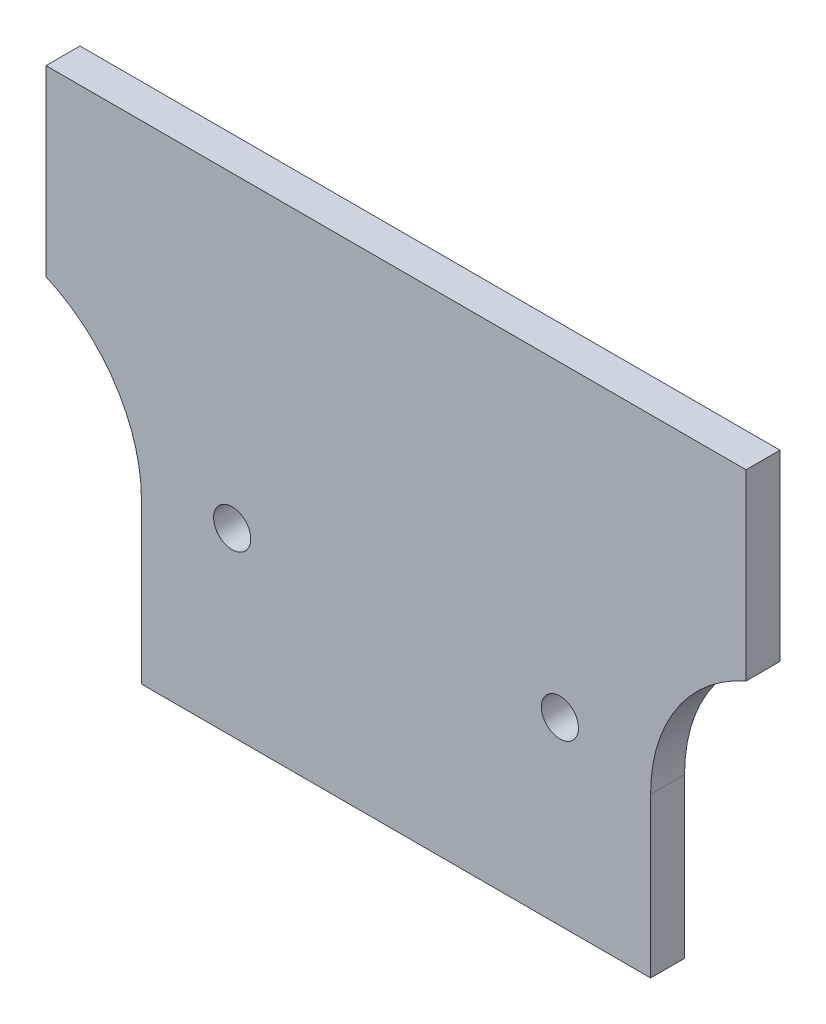
SolidWorks part; units mm, degrees
ref_plane "Front Plane" through (0, 0, 0) normal (0, 0, 1) x (1, 0, 0)
ref_plane "Top Plane" through (0, 0, 0) normal (0, 1, 0) x (1, 0, 0)
ref_plane "Right Plane" through (0, 0, 0) normal (1, 0, 0) x (0, 0, -1)
ref_axis "Axis1" through (0, 0, 0) along (0, 1, 0)
ref_plane "Camera Mount Plane" through (0, 0, 0.8128) normal (0, 0, 1) x (1, 0, 0)
sketch "Sketch1" plane through (0, 0, 0) normal (0, 0, 1) x (1, 0, 0)
  line L0 (5.715, 0) -> (-5.715, 0) construction
  line L2 (-5.715, -3.81) -> (-5.715, 5.08)
  line L3 (-5.715, 5.08) -> (5.715, 5.08)
  line L4 (5.715, -3.81) -> (5.715, 5.08)
  line L5 (0, 5.08) -> (0, -3.81) construction
  line L7 (5.715, -3.81) -> (-5.715, -3.81)
  circle A0 centre (-3.9243, 0.508) radius 0.445
  circle A1 centre (3.9243, 0.508) radius 0.445
  dimension "D1" = 0.508
  dimension "D5" = 0.89
  dimension "D2" = 7.8486
  dimension "D3" = 11.43
  dimension "D4" = 5.08
  dimension "D8" = 3.81
sketch "Sketch3" plane through (0, 0, 0) normal (0, 0, 1) x (1, 0, 0)
  line L0 (8.382, 7.874) -> (-8.382, 7.874)
  line L1 (-8.382, 7.874) -> (-8.382, 3.4919)
  line L2 (-6.096, 0) -> (-6.096, -3.81)
  line L3 (-6.096, -3.81) -> (6.096, -3.81)
  line L4 (0, 7.874) -> (0, 0) construction
  line L5 (6.096, 0) -> (6.096, -3.81)
  line L6 (8.382, 7.874) -> (8.382, 3.4919)
  line L7 (7.874, 7.112) -> (7.874, 3.912)
  line L8 (-7.874, 7.112) -> (-3.874, 7.112)
  line L9 (-7.874, 7.112) -> (-7.874, 3.912)
  line L10 (-7.874, 3.912) -> (-3.874, 3.912)
  line L11 (-3.874, 7.112) -> (-3.874, 3.912)
  line L12 (7.874, 7.112) -> (3.874, 7.112)
  line L13 (3.874, 7.112) -> (3.874, 3.912)
  line L14 (7.874, 3.912) -> (3.874, 3.912)
  line L16 (5.715, -3.81) -> (-5.715, -3.81) construction
  arc A0 (-8.382, 3.4919) -> (-6.096, 0) centre (-9.906, 0) cw
  arc A1 (8.382, 3.4919) -> (6.096, 0) centre (9.906, 0) ccw
  circle A2 centre (-9.906, 0) radius 3.175 construction
  circle A3 centre (9.906, 0) radius 3.175 construction
  dimension "D5" = 6.35
  dimension "D6" = 3.81
  dimension "D7" = 0.635
  dimension "D1" = 4
  dimension "D2" = 3.2
  dimension "D3" = 0.762
  dimension "D4" = 9.906
  dimension "D8" = 7.874
  dimension "D9" = 0.508
  dimension "D10" = 16.764
sketch "Sketch2" plane through (0, 0, 0) normal (0, 0, 1) x (1, 0, 0)
  line L0 (-5.715, -3.81) -> (-5.715, 5.08)
  line L1 (5.715, -3.81) -> (5.715, 5.08)
  line L8 (5.715, -3.81) -> (-5.715, -3.81) construction
  line L14 (-5.715, 5.08) -> (5.715, 5.08) construction
  line L16 (5.715, -3.81) -> (-5.715, -3.81)
  line L22 (-5.715, 5.08) -> (5.715, 5.08)
  circle A0 centre (-3.9243, 0.508) radius 0.445 construction
  circle A1 centre (-3.9243, 0.508) radius 0.445
  circle A2 centre (3.9243, 0.508) radius 0.445 construction
  circle A3 centre (3.9243, 0.508) radius 0.445
extrude "Boss-Extrude1" add sketch "Sketch2" along normal up to surface (0.8128 mm away) up to plane "Camera Mount Plane"
sketch "Sketch4" plane through (0, 0, 0) normal (0, 0, 1) x (1, 0, 0)
  line L6 (8.382, 7.874) -> (-8.382, 7.874)
  line L7 (-8.382, 7.874) -> (-8.382, 3.4919)
  line L8 (-6.096, 0) -> (-6.096, -3.81)
  line L9 (-6.096, -3.81) -> (6.096, -3.81)
  line L10 (6.096, -3.81) -> (6.096, 0)
  line L11 (8.382, 3.4919) -> (8.382, 7.874)
  line L12 (8.382, 7.874) -> (-8.382, 7.874)
  line L13 (-8.382, 7.874) -> (-8.382, 3.4919)
  line L14 (-6.096, 0) -> (-6.096, -3.81)
  line L15 (-6.096, -3.81) -> (6.096, -3.81)
  line L16 (6.096, -3.81) -> (6.096, 0)
  line L17 (8.382, 3.4919) -> (8.382, 7.874)
  circle A0 centre (-3.9243, 0.508) radius 0.445 construction
  circle A1 centre (-3.9243, 0.508) radius 0.445
  arc A2 (-6.096, 0) -> (-8.382, 3.4919) centre (-9.906, 0) ccw
  arc A3 (8.382, 3.4919) -> (6.096, 0) centre (9.906, 0) ccw
  arc A4 (-6.096, 0) -> (-8.382, 3.4919) centre (-9.906, 0) ccw
  arc A5 (8.382, 3.4919) -> (6.096, 0) centre (9.906, 0) ccw
  circle A6 centre (3.9243, 0.508) radius 0.445 construction
  circle A7 centre (3.9243, 0.508) radius 0.445
  dimension "D1" = 0
extrude "Boss-Extrude2" add sketch "Sketch4" along normal up to surface (0.8128 mm away) up to plane "Camera Mount Plane"
sketch "Sketch5" plane through (0, 0, 0.8128) normal (0, 0, 1) x (1, 0, 0)
  line L0 (-7.874, 7.112) -> (-3.874, 7.112) construction
  line L1 (-7.874, 7.112) -> (-7.874, 3.912) construction
  line L2 (-7.874, 3.912) -> (-3.874, 3.912) construction
  line L3 (-3.874, 7.112) -> (-3.874, 3.912) construction
  line L4 (-7.874, 7.112) -> (-3.874, 7.112)
  line L5 (-7.874, 7.112) -> (-7.874, 3.912)
  line L6 (-7.874, 3.912) -> (-3.874, 3.912)
  line L7 (-3.874, 7.112) -> (-3.874, 3.912)
  line L8 (7.874, 7.112) -> (3.874, 7.112) construction
  line L9 (7.874, 7.112) -> (7.874, 3.912) construction
  line L10 (7.874, 3.912) -> (3.874, 3.912) construction
  line L11 (3.874, 7.112) -> (3.874, 3.912) construction
  line L12 (7.874, 7.112) -> (3.874, 7.112)
  line L13 (7.874, 7.112) -> (7.874, 3.912)
  line L14 (7.874, 3.912) -> (3.874, 3.912)
  line L15 (3.874, 7.112) -> (3.874, 3.912)
extrude "Boss-Extrude3" [suppressed] add sketch "Sketch5" along normal blind 0.5
